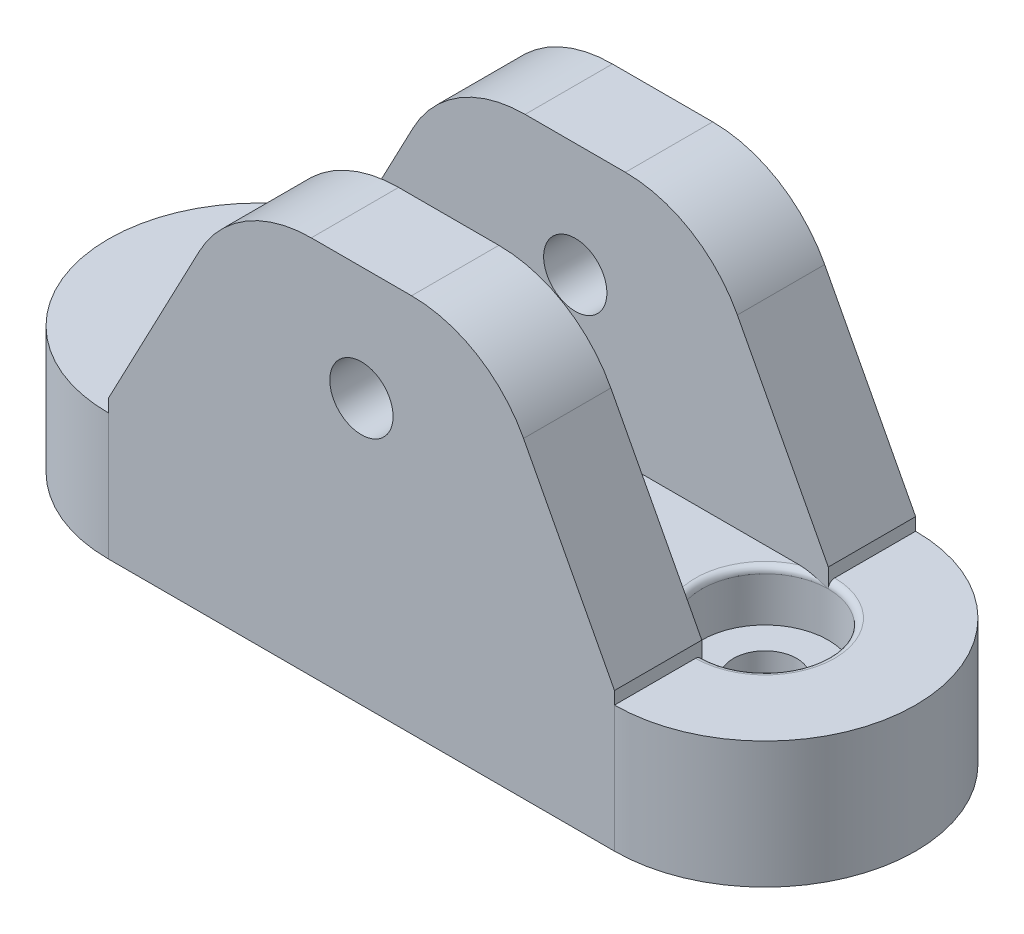
SolidWorks part; units mm, degrees
ref_plane "Alzado" through (0, 0, 0) normal (0, 0, 1) x (1, 0, 0)
ref_plane "Planta" through (0, 0, 0) normal (0, 1, 0) x (1, 0, 0)
ref_plane "Vista lateral" through (0, 0, 0) normal (1, 0, 0) x (0, 0, -1)
sketch "Croquis1" plane through (0, 0, 0) normal (0, 1, 0) x (1, 0, 0)
  line L0 (0, 0) -> (-40, 0) construction
  line L1 (0, -11.9) -> (-40, -11.9)
  line L2 (0, 11.9) -> (-40, 11.9)
  line L3 (-20, 0) -> (-20, 5.9083) construction
  arc A0 (0, -11.9) -> (0, 11.9) centre (0, 0) ccw
  arc A1 (-40, 11.9) -> (-40, -11.9) centre (-40, 0) ccw
  circle A2 centre (-40, 0) radius 2.5
  circle A3 centre (0, 0) radius 2.5
  point P3 (-20, 0)
  dimension "D2" = 40
  dimension "D1" = 23.8
extrude "Saliente-Extruir1" add sketch "Croquis1" along normal blind 10
sketch "Croquis3" plane through (0, 0, 11.9) normal (0, 0, 1) x (1, 0, 0)
  line L0 (-40, 10) -> (-40, 11)
  line L3 (-20, 0) -> (-20, 30) construction
  line L4 (-16.0373, 30) -> (-23.9627, 30)
  line L5 (-32.8119, 24.6575) -> (-40, 11)
  line L7 (-7.1881, 24.6575) -> (0, 11)
  line L8 (0, 10) -> (0, 11)
  line L11 (-40, 10) -> (-40, 0)
  line L12 (-40, 0) -> (0, 0)
  line L13 (0, 10) -> (0, 0)
  circle A0 centre (-20, 21) radius 2.5
  arc A1 (-7.1881, 24.6575) -> (-16.0373, 30) centre (-16.0373, 20) ccw
  arc A2 (-23.9627, 30) -> (-32.8119, 24.6575) centre (-23.9627, 20) ccw
  point P15 (-10, 30)
  point P18 (-30, 30)
  dimension "D5" = 10
  dimension "D6" = 5
  dimension "D1" = 1
  dimension "D2" = 30
  dimension "D3" = 10
  dimension "D4" = 9
extrude "Saliente-Extruir2" add sketch "Croquis3" against normal blind 6.9 contours L7 L8 L13 L12 L11 L0 L5 A2 L4 A1 | A0
pattern_linear "MatrizL1" count 2 spacing 16.9 along (0, 0, -1) of "Saliente-Extruir2"
sketch "Croquis6" plane through (0, 10, 0) normal (0, 1, 0) x (1, 0, 0)
  line L0 (-40, 0) -> (0, 0) construction
  line L1 (-20, 0) -> (-20, 2.9202) construction
  circle A0 centre (-40, 0) radius 5
  circle A1 centre (0, 0) radius 5
  dimension "D1" = 10
extrude "Cortar-Extruir1" cut sketch "Croquis6" against normal mid plane 8
fillet "Redondeo3" radius 0.5 4 edges at (-35, 10, 0) (-45, 10, 0) (5, 10, 0) (-5, 10, 0)
sketch "Croquis7" plane through (0, 10, 0) normal (0, 1, 0) x (1, 0, 0)
  line L0 (-20, 5) -> (-20, -5) construction
  line L1 (-37.7087, 5) -> (-2.2913, 5) construction
  line L2 (-16.0373, -5) -> (-23.9627, -5) construction
